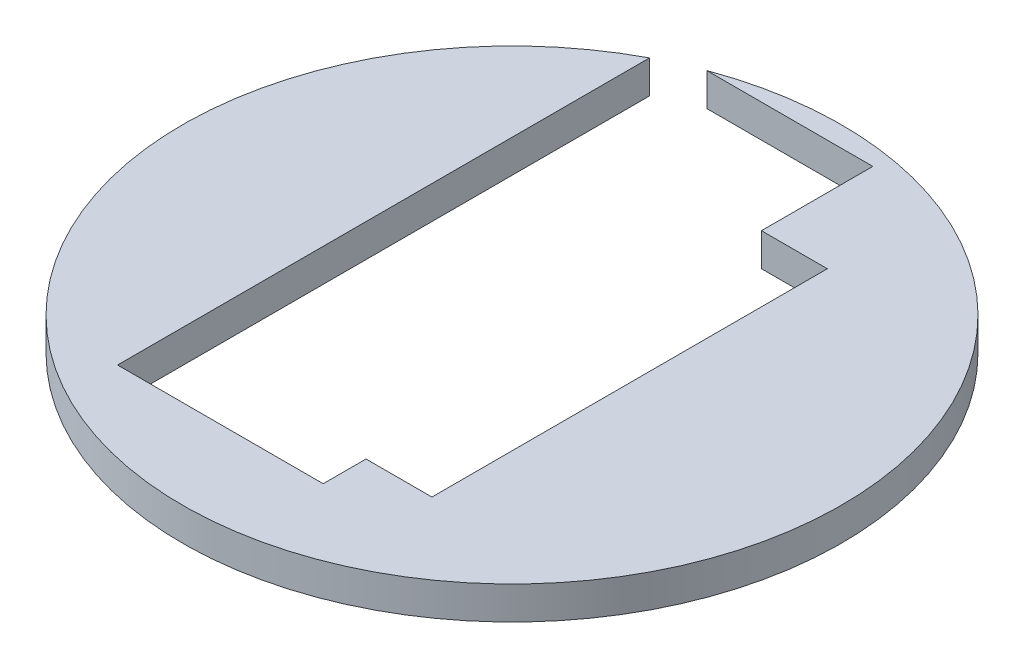
SolidWorks part; units mm, degrees
material "Polylactic Acid (PLA)"
ref_plane "Front Plane" through (0, 0, 0) normal (0, 0, 1) x (1, 0, 0)
ref_plane "Top Plane" through (0, 0, 0) normal (0, 1, 0) x (1, 0, 0)
ref_plane "Right Plane" through (0, 0, 0) normal (1, 0, 0) x (0, 0, -1)
sketch "Sketch1" plane through (0, 0, 0) normal (0, 1, 0) x (1, 0, 0)
  circle A0 centre (0, 0) radius 47.625
  dimension "D1" = 95.25
extrude "Boss-Extrude1" add sketch "Sketch1" against normal blind 12.7
sketch "Sketch2" plane through (0, 0, 0) normal (0, 1, 0) x (1, 0, 0)
  line L0 (0, -50.8) -> (0, 44.45) construction
  line L11 (26.035, 5.08) -> (26.035, -36.0275)
  line L12 (-30.48, 5.08) -> (-26.035, 5.08)
  line L14 (19.685, 25.0825) -> (15.24, 25.0825)
  line L15 (15.24, 25.0825) -> (15.24, 41.7558)
  line L16 (-30.48, 5.08) -> (-30.48, -32.3539)
  line L18 (-19.685, 25.0825) -> (-19.685, 39.8535)
  line L19 (19.685, 25.0825) -> (19.685, 39.8535)
  line L20 (-15.24, 25.0825) -> (-15.24, 41.7558)
  line L21 (-19.685, 25.0825) -> (-15.24, 25.0825)
  line L22 (-26.035, 5.08) -> (-26.035, -36.0275)
  line L23 (30.48, 5.08) -> (30.48, -32.3539)
  line L27 (30.48, 5.08) -> (26.035, 5.08)
  circle A2 centre (0, 0) radius 47.625
  circle A6 centre (0, 0) radius 44.45
  dimension "D1" = 88.9
  dimension "D8" = 95.25
  dimension "D2" = 6.35
  dimension "D3" = 4.445
  dimension "D4" = 4.445
  dimension "D5" = 26.035
  dimension "D6" = 5.08
  dimension "D7" = 20.0025
extrude "Boss-Extrude4" add sketch "Sketch2" along normal blind 12.7 separate body contours A2 A6 | A6 | A6 | A6 | A6 region at (28.223, 0, 14.6101) region at (-28.223, 0, 14.6101) region at (-17.4178, 0, -32.977) region at (17.4178, 0, -32.977) region at (-46.278, 0, 0)
sketch "Sketch10" plane through (0, 0, 0) normal (0, 1, 0) x (1, 0, 0)
  line L0 (3.81, 44.2864) -> (3.81, -44.2864) construction
  line L2 (10.16, -43.2733) -> (10.16, 43.2733)
  line L3 (4.7625, -44.1941) -> (4.7625, 44.1941)
  arc A1 (10.16, 43.2733) -> (3.81, 44.2864) centre (0, 0) ccw
  arc A2 (3.81, -44.2864) -> (10.16, -43.2733) centre (0, 0) ccw
  dimension "D2" = 3.81
  dimension "D1" = 88.9
  dimension "D3" = 6.35
  dimension "D4" = 0.9525
extrude "Boss-Extrude5" add sketch "Sketch10" along normal blind 4.7625 separate body contours L3 L2 region at (7.4518, 0, 0)
sketch "Sketch13" plane through (0, 0, 0) normal (0, 1, 0) x (1, 0, 0)
  line L0 (3.81, -59.065) -> (3.81, 65.3266) construction
  circle A2 centre (-4.9213, 13.5255) radius 8.7312 construction
  circle A3 centre (-4.9213, 13.5255) radius 9.525 construction
  dimension "D2" = 17.4625
  dimension "D3" = 19.05
  dimension "D1" = 3.81
  dimension "D4" = 8.4455
sketch "Sketch14" plane through (0, -12.7, 0) normal (0, -1, 0) x (1, 0, 0)
  line L0 (4.9847, -13.5255) -> (-14.8272, -13.5255) construction
  line L2 (4.9848, -29.7815) -> (-14.8272, -29.7815)
  line L3 (4.9848, -29.7815) -> (4.9847, 23.1775)
  line L4 (4.9847, 23.1775) -> (-14.8272, 23.1775)
  line L5 (-14.8272, -29.7815) -> (-14.8272, 23.1775)
  point P4 (-4.9213, -13.5255)
  dimension "D1" = 52.959
  dimension "D2" = 19.812
  dimension "D3" = 16.256
extrude "Cut-Extrude11" cut sketch "Sketch14" against normal blind 9.2758
sketch "Sketch18" plane through (0, -12.7, 0) normal (0, -1, 0) x (1, 0, 0)
  line L0 (-31.75, 0) -> (31.75, 0) construction
  line L1 (-14.8272, 23.1775) -> (4.9848, 23.1775)
  line L2 (-14.8272, 23.1775) -> (-14.8272, -28.0752)
  line L3 (-11.0057, -29.7815) -> (4.9848, -29.7815)
  line L4 (4.9848, 23.1775) -> (4.9847, 19.05)
  line L5 (4.9848, -19.05) -> (4.9848, -29.7815)
  line L6 (4.9847, 19.05) -> (11.3347, 19.05)
  line L8 (4.9848, -19.05) -> (11.3348, -19.05)
  line L9 (11.3347, 19.05) -> (11.3348, -19.05)
  arc A0 (-11.0057, -29.7815) -> (-14.8272, -28.0752) centre (0, 0) ccw
  dimension "D1" = 6.35
  dimension "D2" = 38.1
  dimension "D3" = 19.05
extrude "Boss-Extrude7" add sketch "Sketch18" along normal blind 3.175 separate body
delete or keep bodies "Body-Delete/Keep 1" type delete bodies bodies 124 118 122
